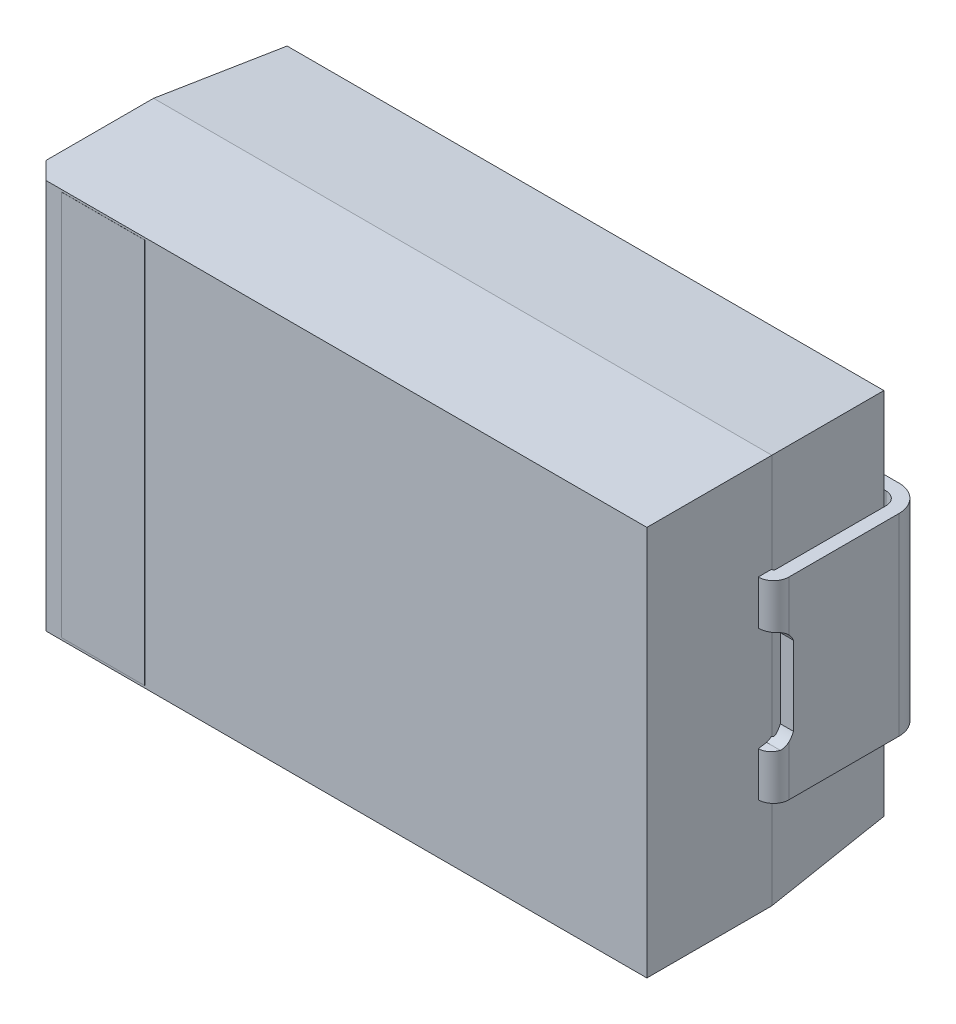
SolidWorks part; units mm, degrees
ref_plane "Спереди" through (0, 0, 0) normal (0, 0, 1) x (1, 0, 0)
ref_plane "Сверху" through (0, 0, 0) normal (0, 1, 0) x (1, 0, 0)
ref_plane "Справа" through (0, 0, 0) normal (1, 0, 0) x (0, 0, -1)
sketch "Эскиз1" plane through (0, 0, 0) normal (0, 0, 1) x (1, 0, 0)
  line L1 (2.25, 2) -> (-2.25, 2)
  line L2 (2.25, 2) -> (2.25, -2)
  line L3 (2.25, -2) -> (-2.25, -2)
  line L4 (-2.25, 2) -> (-2.25, -2)
  line L5 (2.25, 2) -> (-2.25, -2) construction
  line L6 (2.25, -2) -> (-2.25, 2) construction
  point P0 (0, 0)
sketch "Эскиз2" plane through (0, 0, 0) normal (0, 0, 1) x (1, 0, 0)
  line L1 (3.525, 2.225) -> (-3.525, 2.225)
  line L2 (3.525, 2.225) -> (3.525, -2.225)
  line L3 (3.525, -2.225) -> (-3.525, -2.225)
  line L4 (-3.525, 2.225) -> (-3.525, -2.225)
  line L5 (3.525, 2.225) -> (-3.525, -2.225) construction
  line L6 (3.525, -2.225) -> (-3.525, 2.225) construction
  point P0 (0, 0)
sketch "Эскиз3" plane through (0, 0, 0) normal (0, 1, 0) x (1, 0, 0)
  line L0 (-2.429, -0.15) -> (-2.429, 0)
  line L1 (-2.429, 0) -> (-3.4, 0)
  line L2 (-2.429, -0.15) -> (-3.4, -0.15)
  line L4 (-3.55, -0.3) -> (-3.55, -1.555)
  line L5 (-3.7, -0.3) -> (-3.7, -1.555)
  line L7 (-3.525, -1.73) -> (-3.525, -1.58)
  line L9 (0, 0.3291) -> (0, 0.6084) construction
  line L10 (3.525, -1.73) -> (3.525, -1.58)
  line L11 (3.7, -0.3) -> (3.7, -1.555)
  line L12 (3.55, -0.3) -> (3.55, -1.555)
  line L13 (2.429, -0.15) -> (3.4, -0.15)
  line L14 (2.429, 0) -> (3.4, 0)
  line L15 (2.429, -0.15) -> (2.429, 0)
  arc A1 (-3.55, -0.3) -> (-3.4, -0.15) centre (-3.4, -0.3) cw
  arc A2 (-3.4, 0) -> (-3.7, -0.3) centre (-3.4, -0.3) ccw
  arc A3 (-3.55, -1.555) -> (-3.525, -1.58) centre (-3.525, -1.555) ccw
  arc A4 (-3.7, -1.555) -> (-3.525, -1.73) centre (-3.525, -1.555) ccw
  arc A5 (3.7, -1.555) -> (3.525, -1.73) centre (3.525, -1.555) cw
  arc A6 (3.55, -1.555) -> (3.525, -1.58) centre (3.525, -1.555) cw
  arc A7 (3.4, 0) -> (3.7, -0.3) centre (3.4, -0.3) cw
  arc A8 (3.55, -0.3) -> (3.4, -0.15) centre (3.4, -0.3) ccw
extrude "Бобышка-Вытянуть1" add sketch "Эскиз1" against normal blind 0.2 from offset 0.2
extrude "Бобышка-Вытянуть2" add sketch "Эскиз2" along normal blind 1.425 from offset 1.575
extrude "Бобышка-Вытянуть3" add sketch "Эскиз2<2>" against normal blind 1.4 draft 5 from offset 1.575
sketch "Эскиз2<2>" plane through (0, 0, 0) normal (0, 0, 1) x (1, 0, 0) same geometry as "Эскиз2"
sketch "Эскиз6" plane through (0, 0, 0) normal (1, 0, 0) x (0, 0, -1)
  line L0 (-0.7657, 0.45) -> (-0.7657, -0.45)
  line L1 (-0.8937, 0.5982) -> (-1.7534, 0.7244)
  line L3 (-1.7534, 0.7244) -> (-1.7534, -0.7243)
  line L5 (-1.7534, -0.7243) -> (-0.8937, -0.5984)
  arc A2 (-0.8937, 0.5982) -> (-0.7657, 0.45) centre (-0.9154, 0.45) cw
  arc A3 (-0.8937, -0.5984) -> (-0.7657, -0.45) centre (-0.9154, -0.4502) ccw
sketch "Эскиз5" plane through (0, 0, 0) normal (1, 0, 0) x (0, 0, -1)
  line L0 (-1.5039, 0.45) -> (-1.5039, -0.45)
  line L1 (-1.6344, 0.5813) -> (-1.8334, 0.6105)
  line L3 (-1.6344, -0.5813) -> (-1.8334, -0.6105)
  line L4 (-1.8334, -0.6105) -> (-1.8334, 0.6105)
  arc A0 (-1.5039, 0.45) -> (-1.6344, 0.5813) centre (-1.7234, 0.3624) ccw
  arc A1 (-1.5039, -0.45) -> (-1.6344, -0.5813) centre (-1.7234, -0.3624) cw
sketch "Эскиз7" plane through (0, 0, 0) normal (0, 0, 1) x (1, 0, 0)
  line L1 (-3.15, 2.2) -> (-2.2, 2.2)
  line L2 (-3.15, 2.2) -> (-3.15, -2.2)
  line L3 (-3.15, -2.2) -> (-2.2, -2.2)
  line L4 (-2.2, 2.2) -> (-2.2, -2.2)
extrude "Бобышка-Вытянуть4" add sketch "Эскиз3" along normal blind 1.1 and the other way blind 1.1
extrude "Вырез-Вытянуть1" cut sketch "Эскиз6" against normal blind 0.3 from offset 3.525 offset against normal yes
extrude "Вырез-Вытянуть2" cut sketch "Эскиз5" along normal blind 0.5 from offset 3.525
chamfer "Фаска1" distance 0.2 angle 45 1 edges at (-3.525, 0, 3)
chamfer "Фаска2" distance 0.1 angle 45 4 edges at (0, -2, 0) (2.25, 0, 0) (0, 2, 0) (-2.25, 0, 0)
extrude "Бобышка-Вытянуть5" add sketch "Эскиз7" along normal blind 0.001 from vertex separate body starting at point (3.525, -2.225, 3)
